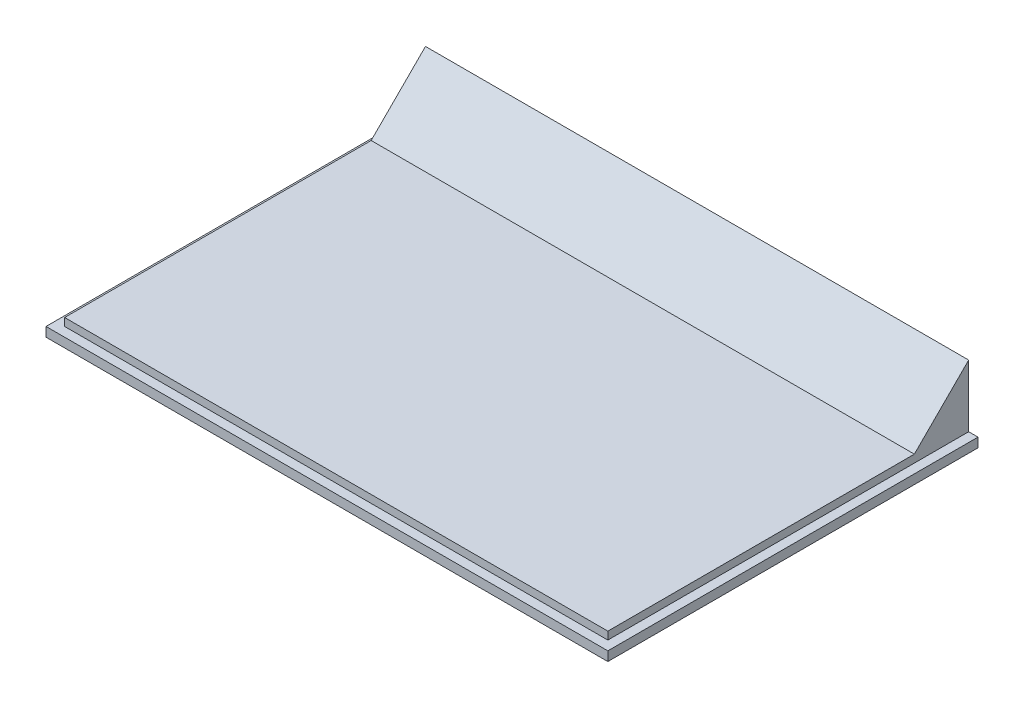
SolidWorks part; units mm, degrees
ref_plane "Přední rovina" through (0, 0, 0) normal (0, 0, 1) x (1, 0, 0)
ref_plane "Horní rovina" through (0, 0, 0) normal (0, 1, 0) x (1, 0, 0)
ref_plane "Pravá rovina" through (0, 0, 0) normal (1, 0, 0) x (0, 0, -1)
sketch "Skica2" plane through (0, 0, 0) normal (0, 1, 0) x (1, 0, 0)
  line L1 (0, 0) -> (72.4, 0)
  line L2 (0, 0) -> (0, 47.7)
  line L3 (0, 47.7) -> (72.4, 47.7)
  line L4 (72.4, 0) -> (72.4, 47.7)
  dimension "D1" = 47.7
  dimension "D2" = 72.4
extrude "Přidat vysunutím1" add sketch "Skica2" along normal blind 1.2
sketch "Skica3" plane through (0, 1.2, 0) normal (0, 1, 0) x (1, 0, 0)
  line L0 (72.4, 47.7) -> (0, 47.7) construction
  line L1 (1.2, 47.7) -> (71.2, 47.7)
  line L2 (1.2, 47.7) -> (1.2, 1.2)
  line L3 (1.2, 1.2) -> (71.2, 1.2)
  line L4 (71.2, 47.7) -> (71.2, 1.2)
  line L5 (0, 47.7) -> (0, 0) construction
  dimension "D1" = 46.5
  dimension "D2" = 70
  dimension "D3" = 1.2
extrude "Přidat vysunutím2" add sketch "Skica3" along normal blind 1
sketch "Skica4" plane through (0, 2.2, 0) normal (0, 1, 0) x (1, 0, 0)
  line L1 (71.2, 47.7) -> (1.2, 47.7)
  line L2 (71.2, 47.7) -> (71.2, 40.7)
  line L3 (71.2, 40.7) -> (1.2, 40.7)
  line L4 (1.2, 47.7) -> (1.2, 40.7)
  line L5 (1.2, 47.7) -> (1.2, 1.2) construction
  dimension "D1" = 7
  dimension "D2" = 70
extrude "Přidat vysunutím3" add sketch "Skica4" along normal blind 7
chamfer "Zkosení2" distance 7 angle 45 1 edges at (36.2, 9.2, -40.7)
